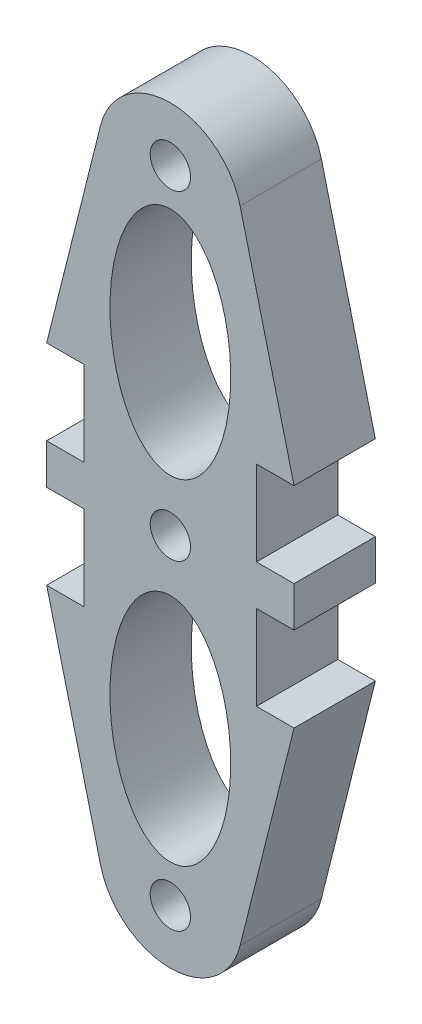
SolidWorks part; units mm, degrees
material "Acrylic (Medium-high impact)"
ref_plane "Front Plane" through (0, 0, 0) normal (0, 0, 1) x (1, 0, 0)
ref_plane "Top Plane" through (0, 0, 0) normal (0, 1, 0) x (1, 0, 0)
ref_plane "Right Plane" through (0, 0, 0) normal (1, 0, 0) x (0, 0, -1)
sketch "Sketch1" plane through (0, 0, 0) normal (0, 0, 1) x (1, 0, 0)
  line L0 (-213.0435, 464.8524) -> (49786.9565, 464.8524) construction
  line L1 (781.4592, 464.8524) -> (778.7592, 464.8524)
  line L2 (781.4592, 464.8524) -> (781.4592, 470.9524)
  line L3 (781.4592, 470.9524) -> (778.7592, 470.9524)
  line L4 (787.6592, -515.9255) -> (787.6592, 49484.0745) construction
  line L5 (-215.2235, 463.4024) -> (49784.7765, 463.4024) construction
  line L6 (793.8592, 470.9524) -> (793.8592, 486.4524) construction
  line L7 (-217.5077, 461.9524) -> (49782.4923, 461.9524) construction
  line L8 (786.2092, -537.0976) -> (786.2092, 49462.9024) construction
  line L9 (789.1092, -536.5976) -> (789.1092, 49463.4024) construction
  line L10 (793.8592, 464.8524) -> (796.5592, 464.8524)
  line L11 (781.4592, 470.9524) -> (793.8592, 470.9524) construction
  line L12 (793.8592, 470.9524) -> (796.5592, 470.9524)
  line L13 (793.8592, 464.8524) -> (793.8592, 470.9524)
  line L14 (778.7592, 464.8524) -> (778.7592, 461.9524)
  line L15 (796.5592, 464.8524) -> (796.5592, 461.9524)
  line L16 (786.2092, 486.4524) -> (782.6401, 486.4524) construction
  line L17 (781.4592, 461.9524) -> (778.7592, 461.9524)
  line L18 (793.8592, 470.9524) -> (793.1379, 470.9192) construction
  line L19 (781.4592, 455.8524) -> (778.7592, 455.8524)
  line L20 (781.4592, 461.9524) -> (781.4592, 455.8524)
  line L21 (793.8592, 461.9524) -> (796.5592, 461.9524)
  line L22 (793.8592, 461.9524) -> (793.8592, 455.8524)
  line L23 (793.8592, 455.8524) -> (796.5592, 455.8524)
  line L24 (778.7592, 470.9524) -> (782.6401, 486.4524)
  line L25 (792.6782, 486.4524) -> (796.5592, 470.9524)
  line L26 (792.6782, 440.3524) -> (796.5592, 455.8524)
  line L27 (789.1092, 440.3524) -> (792.6782, 440.3524) construction
  line L28 (786.2092, 440.3524) -> (782.6401, 440.3524) construction
  line L29 (778.7592, 455.8524) -> (782.6401, 440.3524)
  line L35 (789.1092, 486.4524) -> (792.6782, 486.4524) construction
  arc A0 (782.6401, 486.4524) -> (792.6782, 486.4524) centre (787.6592, 485.1957) cw
  arc A1 (782.6401, 440.3524) -> (792.6782, 440.3524) centre (787.6592, 441.609) ccw
  circle A3 centre (787.6592, 486.4524) radius 1.45
  circle A5 centre (787.6592, 440.3524) radius 1.45
  circle A6 centre (787.6592, 463.4024) radius 1.45
  ellipse E0 centre (787.6592, 475.4481) end of major axis (787.6592, 483.7502) minor radius 4.3465
  ellipse E1 centre (787.6592, 451.3566) end of major axis (787.6592, 443.0545) minor radius 4.3465
  point P10 (778.7592, 463.4024)
  point P19 (796.5592, 463.4024)
  dimension "D1" = 2.9
  dimension "D3" = 6.1
  dimension "D10" = 5.174
  dimension "D2" = 2.7
  dimension "D4" = 23.05
  dimension "D5" = 12.4
  dimension "D6" = 16.6042
  dimension "D7" = 8.693
  dimension "D8" = 2.2937
extrude "Boss-Extrude1" add sketch "Sketch1" along normal blind 5.85 contours L3 A3 A5 region at (782.0271, 467.9024, 0)
